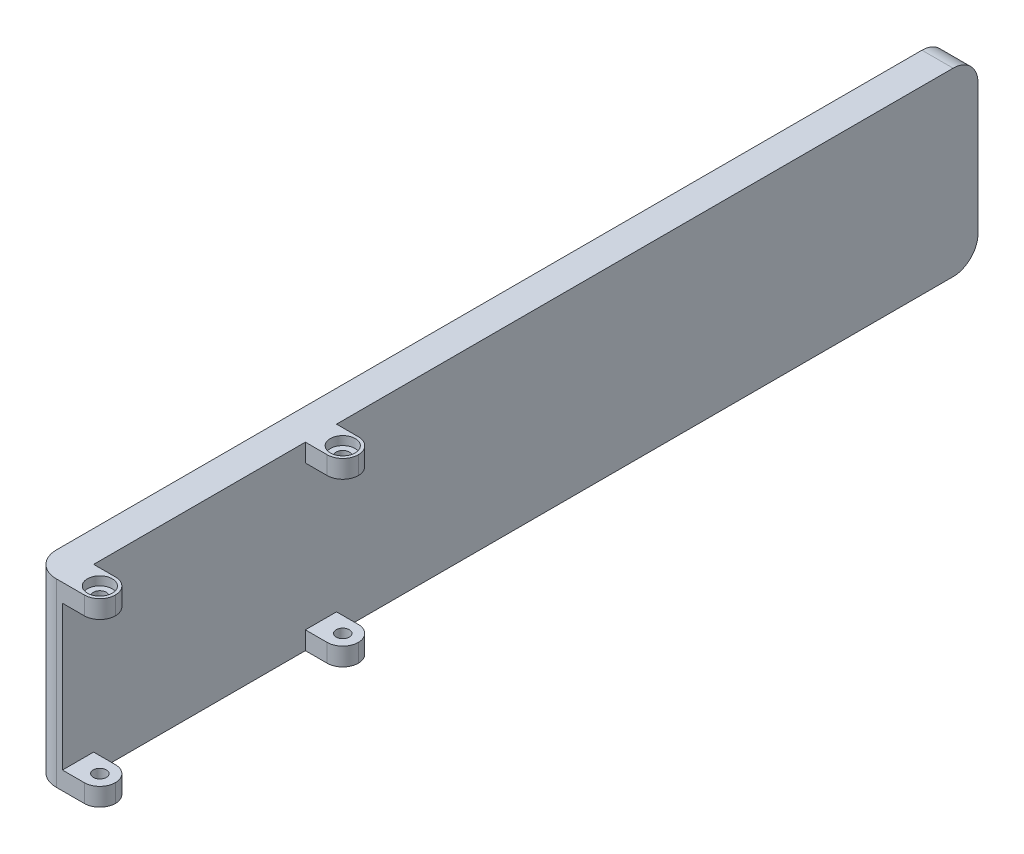
SolidWorks part; units mm, degrees
material "Esun Hard Tough Resin"
ref_plane "Front Plane" through (0, 0, 0) normal (0, 0, 1) x (1, 0, 0)
ref_plane "Top Plane" through (0, 0, 0) normal (0, 1, 0) x (1, 0, 0)
ref_plane "Right Plane" through (0, 0, 0) normal (1, 0, 0) x (0, 0, -1)
sketch "Sketch1" plane through (0, 0, 0) normal (0, 1, 0) x (1, 0, 0)
  line L1 (0, 0) -> (-5, 0)
  line L2 (0, 0) -> (0, 147)
  line L3 (0, 147) -> (-5, 147)
  line L4 (-5, 0) -> (-5, 147)
  dimension "D1" = 5
  dimension "D2" = 147
extrude "Boss-Extrude1" add sketch "Sketch1" along normal blind 29
sketch "Sketch2" plane through (0, 0, 0) normal (1, 0, 0) x (0, 0, -1)
  line L0 (0, 29) -> (147, 29) construction
  line L1 (0, 29) -> (5, 29)
  line L2 (0, 29) -> (0, 26.1)
  line L3 (0, 26.1) -> (5, 26.1)
  line L4 (5, 29) -> (5, 26.1)
  line L5 (39, 29) -> (44, 29)
  line L6 (39, 29) -> (39, 26.1)
  line L7 (39, 26.1) -> (44, 26.1)
  line L8 (44, 29) -> (44, 26.1)
  line L9 (-1000, 14.5) -> (49000, 14.5) construction
  line L10 (0, 29) -> (0, 0) construction
  line L11 (39, 2.9) -> (44, 2.9)
  line L12 (44, 0) -> (44, 2.9)
  line L13 (39, 0) -> (44, 0)
  line L14 (39, 0) -> (39, 2.9)
  line L15 (0, 2.9) -> (5, 2.9)
  line L16 (5, 0) -> (5, 2.9)
  line L17 (0, 0) -> (5, 0)
  line L18 (0, 0) -> (0, 2.9)
  point P12 (2.5, 26.1)
  point P16 (0, 14.5)
  point P17 (41.5, 26.1)
  dimension "D1" = 39
  dimension "D2" = 5
  dimension "D3" = 2.9
extrude "Boss-Extrude2" add sketch "Sketch2" along normal blind 6
sketch "Sketch3" plane through (0, 29, 0) normal (0, 1, 0) x (1, 0, 0)
  line L0 (6, 44) -> (6, 39) construction
  line L1 (6, 44) -> (6, 39) construction
  circle A0 centre (3.5, 41.5) radius 1.05
  circle A1 centre (3.5, 2.5) radius 1.05
  point P8 (6, 41.5)
  dimension "D1" = 2.1
  dimension "D2" = 39
  dimension "D3" = 2.5
extrude "Cut-Extrude1" cut sketch "Sketch3" against normal through all
sketch "Sketch4" plane through (0, 29, 0) normal (0, 1, 0) x (1, 0, 0)
  circle A0 centre (3.5, 2.5) radius 1.05 construction
  circle A1 centre (3.5, 41.5) radius 1.05 construction
  circle A2 centre (3.5, 2.5) radius 1.05 construction
  circle A3 centre (3.5, 41.5) radius 1.05 construction
  circle A4 centre (3.5, 41.5) radius 2
  circle A5 centre (3.5, 2.5) radius 2
  dimension "D1" = 4
extrude "Cut-Extrude2" cut sketch "Sketch4" against normal blind 1.4
ref_plane "Plane1" through (0, 14.5, 0) normal (0, 1, 0) x (1, 0, 0)
mirror "Mirror2" about plane through (0, 14.5, 0) normal (0, 1, 0) of "Cut-Extrude2"
fillet "Fillet1" radius 4 3 edges at (-2.5, 0, -147) (-2.5, 29, -147) (-5, 14.5, 0)
fillet "Fillet2" radius 2.5 8 edges at (6, 1.45, -5) (6, 1.45, 0) (6, 1.45, -44) (6, 1.45, -39) (6, 27.55, -44) (6, 27.55, -39) (6, 27.55, -5) (6, 27.55, 0)
